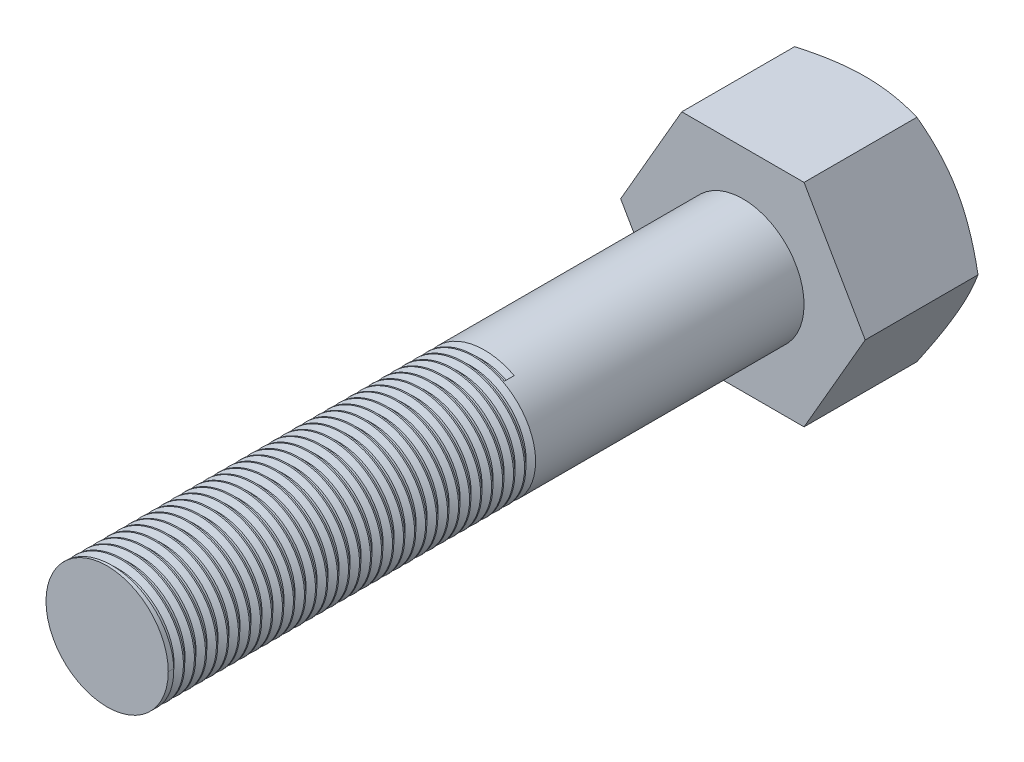
SolidWorks part; units mm, degrees
material "Plain Carbon Steel"
ref_plane "Front Plane" through (0, 0, 0) normal (0, 0, 1) x (1, 0, 0)
ref_plane "Top Plane" through (0, 0, 0) normal (0, 1, 0) x (1, 0, 0)
ref_plane "Right Plane" through (0, 0, 0) normal (1, 0, 0) x (0, 0, -1)
sketch "Sketch1" plane through (0, 0, 0) normal (0, 1, 0) x (1, 0, 0)
  line L0 (0, 0) -> (0, 31)
  line L1 (0, 31) -> (5, 31)
  line L2 (5, 31) -> (5, 26)
  line L3 (5, 26) -> (2.5, 26)
  line L4 (2.5, 26) -> (2.5, 0)
  line L5 (2.5, 0) -> (0, 0)
  dimension "D1" = 26
  dimension "D2" = 2.5
  dimension "D3" = 5
  dimension "D4" = 5
revolve "Revolve1" add sketch "Sketch1" angle 360 about L0
sketch "Sketch2" plane through (0, 0, -31) normal (0, 0, -1) x (-1, 0, 0)
  line L1 (-5, 0) -> (-2.5, -4.3301)
  line L2 (-2.5, -4.3301) -> (2.5, -4.3301)
  line L3 (2.5, -4.3301) -> (5, 0)
  line L4 (5, 0) -> (2.5, 4.3301)
  line L5 (2.5, 4.3301) -> (-2.5, 4.3301)
  line L6 (-2.5, 4.3301) -> (-5, 0)
  circle A0 centre (0, 0) radius 4.3301 construction
  dimension "D1" = 10
extrude "Cut-Extrude2" cut sketch "Sketch2" against normal blind 10 flip side to cut
sketch "Sketch4" plane through (0, 0, -31) normal (0, 0, -1) x (-1, 0, 0)
  line L0 (5, 0) -> (2.5, 4.3301) construction
  circle A0 centre (0, 0) radius 4.3301
extrude "Cut-Extrude6" cut sketch "Sketch4" against normal blind 2 draft 60 flip side to cut contours A0
thread "Thread2" pitch 0.45 method cut profile "Thread Profile2" start angle 0, offset 0, length 15, pitch 0.45, diameter 5
ref_plane "Plane2" through (-2.5, 0, 0) normal (0, -1, 0) x (-1, 0, 0)
sketch "Thread Profile2" plane through (-2.5, 0, 0) normal (0, -1, 0) x (-1, 0, 0)
  line L0 (0, 0) -> (0, 0.45) construction
  line L11 (0, 0) -> (0, 0.3937)
  line L12 (0, 0.3937) -> (-0.2436, 0.2531)
  line L13 (-0.2436, 0.2531) -> (-0.2436, 0.1406)
  line L15 (-0.2436, 0.1406) -> (0, 0)
  line L17 (-0.2436, 0.1969) -> (0, 0.1969) construction
  point P2 (0, 0)
  dimension "Pitch" = 0.45
  dimension "Profile_Angle" = 60
  dimension "Profile_Land" = 0.1125
  dimension "Profile_Height" = 0.2436
